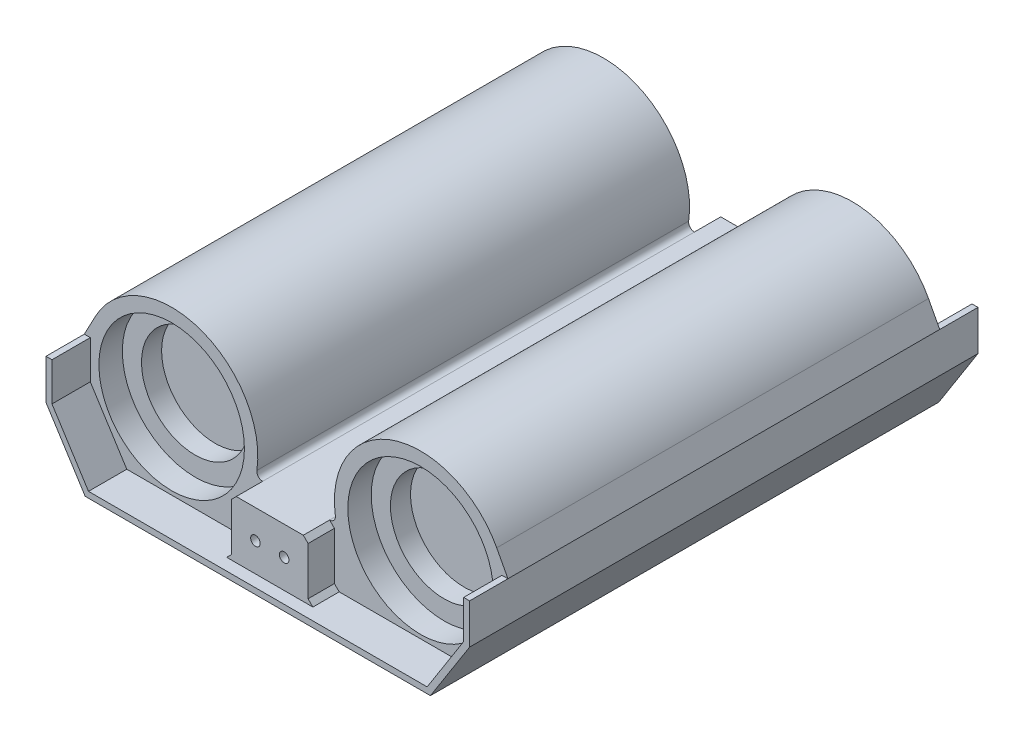
SolidWorks part; units mm, degrees
material "Thornel VCB-20 Carbon Cloth"
ref_plane "Front Plane" through (0, 0, 0) normal (0, 0, 1) x (1, 0, 0)
ref_plane "Top Plane" through (0, 0, 0) normal (0, 1, 0) x (1, 0, 0)
ref_plane "Right Plane" through (0, 0, 0) normal (1, 0, 0) x (0, 0, -1)
sketch "Sketch3" plane through (0, 0, 0) normal (0, 0, 1) x (1, 0, 0)
  line L0 (-7.5, -25) -> (7.5, -25) construction
  line L3 (-20, -10) -> (20, -10)
  line L4 (-20, -40) -> (-20, -10)
  line L5 (-20, -40) -> (20, -40)
  line L6 (20, -40) -> (20, -10)
  line L7 (0, -40) -> (0, -10) construction
  line L8 (0, -10) -> (0, 0) construction
  circle A2 centre (7.5, -25) radius 2.5
  circle A3 centre (-7.5, -25) radius 2.5
  point P11 (0, -25)
  dimension "D4" = 5
  dimension "D5" = 5
  dimension "D1" = 15
  dimension "D2" = 40
  dimension "D3" = 30
  dimension "D6" = 15
  dimension "D7" = 10
extrude "Boss-Extrude2" add sketch "Sketch3" along normal blind 6.25
sketch "Sketch4" plane through (0, 0, 6.25) normal (0, 0, 1) x (1, 0, 0)
  line L0 (20, -40) -> (20, -10) construction
  line L1 (-20, -40) -> (20, -40)
  line L2 (-20, -40) -> (-20, -33.75)
  line L3 (-20, -33.75) -> (20, -33.75)
  line L4 (20, -40) -> (20, -33.75)
  dimension "D1" = 6.25
extrude "Boss-Extrude3" add sketch "Sketch4" along normal blind 7.5
sketch "Sketch5" plane through (0, 0, 13.75) normal (0, 0, 1) x (1, 0, 0)
  line L1 (-20, -40) -> (-88.4287, -40)
  line L12 (-110.625, -10.9092) -> (-90.1451, -43.125)
  line L13 (0, -33.75) -> (0, -40) construction
  line L27 (-107.5, -10) -> (-88.4287, -40)
  line L29 (-107.5, 10) -> (-107.5, -10)
  line L30 (-107.5, 10) -> (-110.625, 10)
  line L31 (-110.625, 10) -> (-110.625, -10.9092)
  line L32 (110.625, 10) -> (110.625, -10.9092)
  line L33 (107.5, 10) -> (110.625, 10)
  line L34 (107.5, 10) -> (107.5, -10)
  line L35 (107.5, -10) -> (88.4287, -40)
  line L36 (110.625, -10.9092) -> (90.1451, -43.125)
  line L38 (20, -40) -> (88.4287, -40)
  line L39 (-90.1451, -43.125) -> (90.1451, -43.125)
  line L40 (-20, -40) -> (20, -40) construction
  line L41 (-20, -40) -> (20, -40)
  arc A1 (-104.9218, -10.3078) -> (-55, -40) centre (-65, 0) ccw construction
  arc A4 (104.9218, -10.3078) -> (55, -40) centre (65, 0) cw construction
  dimension "D3" = 3.125
  dimension "D2" = 3.125
  dimension "D4" = 3.125
  dimension "D7" = 20
  dimension "D1" = 10
  dimension "D5" = 42.5
  dimension "D6" = 50
  dimension "D8" = 65
extrude "Boss-Extrude4" add sketch "Sketch5" against normal blind 20
chamfer "Chamfer1" distance 2.5 angle 45 4 edges at (-20, -10, 3.125) (20, -10, 3.125) (-20, -40, 6.875) (20, -40, 6.875)
sketch "Sketch6" plane through (0, 0, 13.75) normal (0, 0, 1) x (1, 0, 0)
  line L0 (-110.625, 10) -> (-104.7676, 21.0604)
  line L1 (-90.1451, -43.125) -> (90.1451, -43.125) construction
  line L2 (-110.625, -10.9092) -> (-90.1451, -43.125) construction
  line L3 (-110.625, 10) -> (-110.625, -10.9092) construction
  line L4 (-90.1451, -43.125) -> (90.1451, -43.125)
  line L5 (-110.625, -10.9092) -> (-90.1451, -43.125)
  line L6 (-110.625, 10) -> (-110.625, -10.9092)
  line L7 (0, 0) -> (0, -43.125) construction
  line L9 (-65, 0) -> (0, 0) construction
  line L11 (17.5, -10) -> (-17.5, -10)
  line L15 (110.625, 10) -> (110.625, -10.9092)
  line L16 (110.625, -10.9092) -> (90.1451, -43.125)
  line L17 (110.625, 10) -> (104.7676, 21.0604)
  circle A1 centre (-65, 0) radius 38
  arc A3 (-20.4793, -6.5503) -> (-104.7676, 21.0604) centre (-65, 0) ccw
  arc A5 (-20.4793, -6.5503) -> (-17.5, -10) centre (-17.5, -6.9886) ccw
  arc A6 (20.4793, -6.5503) -> (17.5, -10) centre (17.5, -6.9886) cw
  arc A7 (20.4793, -6.5503) -> (104.7676, 21.0604) centre (65, 0) cw
  circle A8 centre (65, 0) radius 38
  point P26 (0, -10)
  dimension "D1" = 76
  dimension "D2" = 65
  dimension "D3" = 45
extrude "Boss-Extrude5" add sketch "Sketch6" along normal blind 12.25
sketch "Sketch8" plane through (0, 0, 26) normal (0, 0, 1) x (1, 0, 0)
  line L0 (-65, 0) -> (0, 0) construction
  line L1 (0, 0) -> (0, -43.125) construction
  line L2 (-90.1451, -43.125) -> (90.1451, -43.125) construction
  line L13 (-104.7676, 21.0604) -> (-110.625, 10)
  line L14 (-110.625, 10) -> (-110.625, -10.9092)
  line L15 (-110.625, -10.9092) -> (-90.1451, -43.125)
  line L16 (-90.1451, -43.125) -> (90.1451, -43.125)
  line L17 (90.1451, -43.125) -> (110.625, -10.9092)
  line L18 (110.625, -10.9092) -> (110.625, 10)
  line L19 (110.625, 10) -> (104.7676, 21.0604)
  line L21 (17.5, -10) -> (-17.5, -10)
  line L23 (-104.7676, 21.0604) -> (-110.625, 10)
  line L24 (-110.625, 10) -> (-110.625, -10.9092)
  line L25 (-110.625, -10.9092) -> (-90.1451, -43.125)
  line L26 (-90.1451, -43.125) -> (90.1451, -43.125)
  line L27 (90.1451, -43.125) -> (110.625, -10.9092)
  line L28 (110.625, -10.9092) -> (110.625, 10)
  line L29 (110.625, 10) -> (104.7676, 21.0604)
  line L31 (17.5, -10) -> (-17.5, -10)
  circle A0 centre (-65, 0) radius 28
  circle A1 centre (65, 0) radius 28
  arc A5 (-20.4793, -6.5503) -> (-104.7676, 21.0604) centre (-65, 0) ccw
  arc A6 (104.7676, 21.0604) -> (20.4793, -6.5503) centre (65, 0) ccw
  arc A7 (17.5, -10) -> (20.4793, -6.5503) centre (17.5, -6.9886) ccw
  arc A8 (-20.4793, -6.5503) -> (-17.5, -10) centre (-17.5, -6.9886) ccw
  arc A9 (-20.4793, -6.5503) -> (-104.7676, 21.0604) centre (-65, 0) ccw
  arc A10 (104.7676, 21.0604) -> (20.4793, -6.5503) centre (65, 0) ccw
  arc A11 (17.5, -10) -> (20.4793, -6.5503) centre (17.5, -6.9886) ccw
  arc A12 (-20.4793, -6.5503) -> (-17.5, -10) centre (-17.5, -6.9886) ccw
  dimension "D1" = 56
  dimension "D2" = 0
extrude "Boss-Extrude7" add sketch "Sketch8" along normal blind 10.5
sketch "Sketch9" plane through (0, 0, 36.5) normal (0, 0, 1) x (1, 0, 0)
  line L0 (0, 0) -> (0, -43.125) construction
  line L1 (-90.1451, -43.125) -> (90.1451, -43.125) construction
  circle A2 centre (65, 0) radius 31.125
  circle A3 centre (-65, 0) radius 31.125
  circle A4 centre (-65, 0) radius 31.125
  dimension "D1" = 3.125
extrude "Boss-Extrude8" add sketch "Sketch9" along normal blind 3.125
fillet "Fillet1" radius 4 2 edges at (33.875, 0, 36.5) (-33.875, 0, 36.5)
sketch "Sketch10" plane through (0, 0, 36.5) normal (0, 0, 1) x (1, 0, 0)
  line L10 (-104.7676, 21.0604) -> (-110.625, 10)
  line L11 (-110.625, 10) -> (-110.625, -10.9092)
  line L12 (-110.625, -10.9092) -> (-90.1451, -43.125)
  line L13 (-90.1451, -43.125) -> (90.1451, -43.125)
  line L14 (90.1451, -43.125) -> (110.625, -10.9092)
  line L15 (110.625, -10.9092) -> (110.625, 10)
  line L16 (110.625, 10) -> (104.7676, 21.0604)
  line L18 (17.5, -10) -> (-17.5, -10)
  line L20 (-104.7676, 21.0604) -> (-110.625, 10)
  line L21 (-110.625, 10) -> (-110.625, -10.9092)
  line L22 (-110.625, -10.9092) -> (-90.1451, -43.125)
  line L23 (-90.1451, -43.125) -> (-47.5, -43.125)
  line L24 (90.1451, -43.125) -> (110.625, -10.9092)
  line L25 (110.625, -10.9092) -> (110.625, 10)
  line L26 (110.625, 10) -> (104.7676, 21.0604)
  line L28 (17.5, -10) -> (-17.5, -10)
  line L30 (-47.5, -43.125) -> (-47.5, -40)
  line L31 (47.5, -43.125) -> (47.5, -40)
  line L32 (47.5, -43.125) -> (90.1451, -43.125)
  line L33 (47.5, -40) -> (88.4287, -40)
  line L40 (-102.006, 19.5978) -> (-107.5, 9.2236)
  line L41 (-107.5, 9.2236) -> (-107.5, -10)
  line L42 (-107.5, -10) -> (-88.4287, -40)
  line L43 (-88.4287, -40) -> (88.4287, -40)
  line L44 (88.4287, -40) -> (107.5, -10)
  line L45 (107.5, -10) -> (107.5, 9.2236)
  line L46 (107.5, 9.2236) -> (102.006, 19.5978)
  line L48 (17.5, -13.125) -> (-17.5, -13.125)
  line L50 (-102.006, 19.5978) -> (-107.5, 9.2236)
  line L51 (-107.5, 9.2236) -> (-107.5, -10)
  line L52 (-107.5, -10) -> (-88.4287, -40)
  line L53 (-88.4287, -40) -> (-47.5, -40)
  line L54 (88.4287, -40) -> (107.5, -10)
  line L55 (107.5, -10) -> (107.5, 9.2236)
  line L56 (107.5, 9.2236) -> (102.006, 19.5978)
  line L58 (17.5, -13.125) -> (-17.5, -13.125)
  arc A4 (-20.4793, -6.5503) -> (-104.7676, 21.0604) centre (-65, 0) ccw
  arc A5 (104.7676, 21.0604) -> (20.4793, -6.5503) centre (65, 0) ccw
  arc A6 (17.5, -10) -> (20.4793, -6.5503) centre (17.5, -6.9886) ccw
  arc A7 (-20.4793, -6.5503) -> (-17.5, -10) centre (-17.5, -6.9886) ccw
  arc A8 (-20.4793, -6.5503) -> (-104.7676, 21.0604) centre (-65, 0) ccw
  arc A9 (104.7676, 21.0604) -> (20.4793, -6.5503) centre (65, 0) ccw
  arc A10 (17.5, -10) -> (20.4793, -6.5503) centre (17.5, -6.9886) ccw
  arc A11 (-20.4793, -6.5503) -> (-17.5, -10) centre (-17.5, -6.9886) ccw
  arc A16 (-23.571, -6.0954) -> (-102.006, 19.5978) centre (-65, 0) ccw
  arc A17 (102.006, 19.5978) -> (23.571, -6.0954) centre (65, 0) ccw
  arc A18 (17.5, -13.125) -> (23.571, -6.0954) centre (17.5, -6.9886) ccw
  arc A19 (-23.571, -6.0954) -> (-17.5, -13.125) centre (-17.5, -6.9886) ccw
  arc A20 (-23.571, -6.0954) -> (-102.006, 19.5978) centre (-65, 0) ccw
  arc A21 (102.006, 19.5978) -> (23.571, -6.0954) centre (65, 0) ccw
  arc A22 (17.5, -13.125) -> (23.571, -6.0954) centre (17.5, -6.9886) ccw
  arc A23 (-23.571, -6.0954) -> (-17.5, -13.125) centre (-17.5, -6.9886) ccw
  dimension "D3" = 47.5
  dimension "D4" = 47.5
  dimension "D1" = 0
  dimension "D2" = 3.125
extrude "Boss-Extrude9" add sketch "Sketch10" along normal blind 90
mirror "Mirror1" about plane through (-65, 0, 126.5) normal (0, 0, 1) of "Boss-Extrude2", "Boss-Extrude3", "Boss-Extrude4", "Chamfer1", "Boss-Extrude5", "Boss-Extrude7", "Boss-Extrude8", "Fillet1", "Boss-Extrude9"
ref_plane "Plane1" through (0, 0, 126.5) normal (0, 0, -1) x (-1, 0, 0)
sketch "Sketch12" plane through (0, 0, 253) normal (0, 0, 1) x (1, 0, 0)
  line L8 (-20, -12.5) -> (-20, -37.5)
  line L9 (-20, -37.5) -> (-22.5, -40)
  line L10 (-22.5, -40) -> (22.5, -40)
  line L11 (22.5, -40) -> (20, -37.5)
  line L12 (20, -37.5) -> (20, -12.5)
  line L13 (20, -12.5) -> (17.5, -10)
  line L14 (17.5, -10) -> (-17.5, -10)
  line L15 (-17.5, -10) -> (-20, -12.5)
  line L16 (-20, -12.5) -> (-20, -37.5)
  line L17 (-20, -37.5) -> (-22.5, -40)
  line L18 (-22.5, -40) -> (22.5, -40)
  line L19 (22.5, -40) -> (20, -37.5)
  line L20 (20, -37.5) -> (20, -12.5)
  line L21 (20, -12.5) -> (17.5, -10)
  line L22 (17.5, -10) -> (-17.5, -10)
  line L23 (-17.5, -10) -> (-20, -12.5)
  circle A0 centre (7.5, -25) radius 2.5 construction
  circle A1 centre (-7.5, -25) radius 2.5 construction
  circle A2 centre (7.5, -25) radius 2.5
  circle A3 centre (-7.5, -25) radius 2.5
  dimension "D1" = 0
extrude "Boss-Extrude10" add sketch "Sketch12" against normal blind 30
mirror "Mirror2" about plane through (0, 0, 126.5) normal (0, 0, -1) of "Boss-Extrude10"
sketch "Sketch13" plane through (0, 0, 0) normal (1, 0, 0) x (0, 0, -1)
  line L0 (-216.5, -43.125) -> (-41.5, -43.125)
  line L1 (-36.5, -38.125) -> (-36.5, -25.2895)
  line L2 (-36.5, 35.0281) -> (-36.5, -35.0281) construction
  line L3 (-41.5, -20.2895) -> (-126.5, -20.2895)
  arc A0 (-36.5, -25.2895) -> (-41.5, -20.2895) centre (-41.5, -25.2895) ccw
  arc A1 (-41.5, -43.125) -> (-36.5, -38.125) centre (-41.5, -38.125) ccw
  point P10 (-36.5, -20.2895)
  point P13 (-36.5, -43.125)
  dimension "D1" = 5
sketch "Sketch14" plane through (0, -43.125, 0) normal (0, -1, 0) x (1, 0, 0)
  line L0 (0, 259.25) -> (0, 237.75) construction
  line L1 (-90.1451, 259.25) -> (90.1451, 259.25) construction
  line L2 (-10, 237.75) -> (10, 237.75) construction
  line L3 (-47.5, 126.5) -> (47.5, 126.5) construction
  line L4 (-47.5, 216.5) -> (-47.5, 36.5) construction
  line L5 (47.5, 216.5) -> (47.5, 36.5) construction
  line L6 (-10, 15.25) -> (10, 15.25) construction
  line L7 (0, -6.25) -> (0, 15.25) construction
  circle A0 centre (10, 237.75) radius 2.5
  circle A1 centre (-10, 237.75) radius 2.5
  circle A2 centre (-10, 15.25) radius 2.5
  circle A3 centre (10, 15.25) radius 2.5
  dimension "D3" = 5
  dimension "D1" = 21.5
  dimension "D2" = 10
extrude "Cut-Extrude1" cut sketch "Sketch14" against normal blind 10
sketch "Sketch16" plane through (0, 0, 0) normal (1, 0, 0) x (0, 0, -1)
  line L0 (-216.5, -41.5625) -> (-36.5, -41.5625) construction
  line L1 (-216.5, -43.125) -> (-216.5, -40) construction
  line L2 (-36.5, -43.125) -> (-36.5, -40) construction
  line L3 (-215.5, -41.0625) -> (-215.5, -40)
  line L4 (-36.5, -42.0625) -> (-216.5, -42.0625)
  line L5 (-36.5, -42.0625) -> (-36.5, -41.0625)
  line L6 (-36.5, -41.0625) -> (-215.5, -41.0625)
  line L7 (-216.5, -42.0625) -> (-216.5, -41.0625)
  line L8 (-36.5, -42.0625) -> (-126.5, -41.5625) construction
  line L9 (-36.5, -41.0625) -> (-216.5, -42.0625) construction
  line L10 (-216.5, -40) -> (-36.5, -40) construction
  line L11 (-215.5, -40) -> (-216.5, -40)
  line L12 (-216.5, -40) -> (-216.5, -10) construction
  line L13 (-216.5, -40) -> (-216.5, -41.0625)
  point P6 (-126.5, -41.5625)
  dimension "D1" = 1
  dimension "D2" = 1
extrude "Cut-Extrude2" cut sketch "Sketch16" along normal mid plane 100
sketch "Sketch17" plane through (-47.5, 0, 0) normal (1, 0, 0) x (0, 0, -1)
  line L0 (-214.5, -41.0625) -> (-214.5, -34.8273)
  line L1 (-36.5, -41.0625) -> (-215.5, -41.0625) construction
  line L2 (-214.5, -34.8273) -> (-215.5, -34.8273)
  line L3 (-215.5, -34.8273) -> (-215.5, -41.0625)
  line L4 (-216.5, -40) -> (-216.5, -10) construction
  line L5 (-215.5, -41.0625) -> (-214.5, -41.0625)
  dimension "D1" = 1
  dimension "D2" = 1
extrude "Boss-Extrude11" add sketch "Sketch17" against normal blind 5
fillet "Fillet2" radius 0.5 2 edges at (-50, -40, 214.5) (-48.75, -41.0625, 215.5)
mirror "Mirror3" about plane through (0, 0, 0) normal (1, 0, 0) of "Cut-Extrude2", "Boss-Extrude11"
fillet "Fillet3" radius 0.5 2 edges at (48.75, -41.0625, 215.5) (50, -40, 214.5)
equation "\"a\"=3.125"
equation "\"D3@Sketch5\"=\"a\""
equation "\"D2@Sketch5\"=\"a\""
equation "\"D4@Sketch5\"=\"a\""
